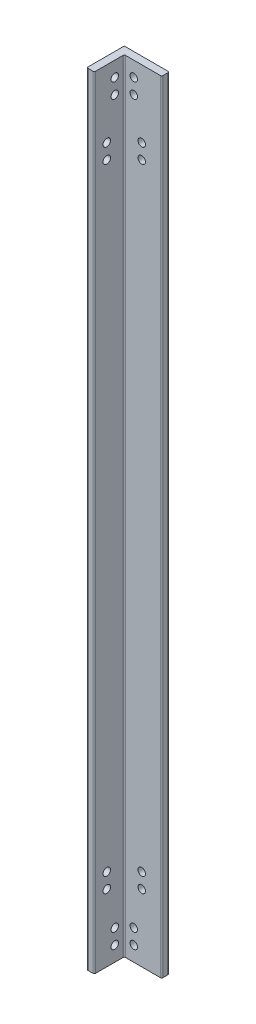
SolidWorks part; units mm, degrees
material "7075-T6 (SN)"
ref_plane "Front Plane" through (0, 0, 0) normal (0, 0, 1) x (1, 0, 0)
ref_plane "Top Plane" through (0, 0, 0) normal (0, 1, 0) x (1, 0, 0)
ref_plane "Right Plane" through (0, 0, 0) normal (1, 0, 0) x (0, 0, -1)
sketch "Sketch1" plane through (0, 0, 0) normal (0, 0, 1) x (1, 0, 0)
  line L0 (-2.6571, 19.3571) -> (-2.6571, -293.6429)
  line L1 (-2.6571, -293.6429) -> (0.3429, -293.6429)
  line L2 (0.3429, -293.6429) -> (0.3429, 19.3571)
  line L3 (0.3429, 19.3571) -> (-2.6571, 19.3571)
  line L4 (0.3429, 19.3571) -> (15.3429, 19.3571)
  line L5 (15.3429, 19.3571) -> (15.3429, -293.6429)
  line L6 (15.3429, -293.6429) -> (0.3429, -293.6429)
  line L7 (0.3429, 19.3571) -> (0.3429, -293.6429)
  circle A0 centre (4.1429, 13.3571) radius 1.5
  circle A1 centre (4.1429, -287.6429) radius 1.5
  circle A2 centre (4.1429, 7.3571) radius 1.5
  circle A3 centre (4.1429, -281.6429) radius 1.5
  circle A4 centre (7.3429, -266.6429) radius 1.5
  circle A5 centre (7.3429, -260.6429) radius 1.5
  circle A6 centre (7.3429, -13.6429) radius 1.5
  circle A7 centre (7.3429, -7.6429) radius 1.5
  dimension "D3" = 6
  dimension "D7" = 3
  dimension "D10" = 3.8
  dimension "D12" = 3.8
  dimension "D4" = 3
  dimension "D5" = 3
  dimension "D6" = 3
  dimension "D17" = 3
  dimension "D18" = 3
  dimension "D22" = 3
  dimension "D23" = 3
  dimension "D1" = 301
  dimension "D2" = 6
  dimension "D8" = 6
  dimension "D9" = 6
  dimension "D11" = 3.8
  dimension "D13" = 3.8
  dimension "D14" = 3
  dimension "D15" = 15
  dimension "D16" = 6
  dimension "D19" = 15
  dimension "D20" = 7
  dimension "D21" = 7
  dimension "D24" = 6
  dimension "D25" = 15
  dimension "D26" = 7
  dimension "D27" = 7
extrude "Boss-Extrude2" add sketch "Sketch1" along normal blind 3 contours L6 L5 L4 L2 A1 A0 region at (7.8685, -137.1429, 0)
extrude "Boss-Extrude3" add sketch "Sketch1<4>" along normal blind 15 contours L2 L3 L0 L1 region at (-1.1571, -137.1429, 0)
sketch "Sketch1<4>" plane through (0, 0, 0) normal (0, 0, 1) x (1, 0, 0) same geometry as "Sketch1"
sketch "Sketch2" plane through (-2.6571, 0, 0) normal (-1, 0, 0) x (0, 0, 1)
  line L0 (15, 19.3571) -> (0, 19.3571) construction
  line L2 (15, -293.6429) -> (0, -293.6429) construction
  line L5 (0, -9.9) -> (0, 9.9) construction
  circle A0 centre (6.8, 13.3571) radius 1.5
  circle A1 centre (6.8, -287.6429) radius 1.5
  circle A2 centre (6.8, -281.6429) radius 1.5
  circle A3 centre (6.8, 7.3571) radius 1.5
  circle A4 centre (10, -266.6429) radius 1.5
  circle A5 centre (10, -260.6429) radius 1.5
  circle A6 centre (10, -13.6429) radius 1.5
  circle A7 centre (10, -7.6429) radius 1.5
  dimension "D1" = 3
  dimension "D4" = 3
  dimension "D7" = 3
  dimension "D12" = 3
  dimension "D15" = 3
  dimension "D16" = 3
  dimension "D23" = 3
  dimension "D24" = 3
  dimension "D2" = 6
  dimension "D3" = 6.8
  dimension "D5" = 6
  dimension "D6" = 6.8
  dimension "D8" = 6
  dimension "D9" = 6.8
  dimension "D10" = 6
  dimension "D11" = 6.8
  dimension "D13" = 10
  dimension "D14" = 10
  dimension "D17" = 15
  dimension "D18" = 6
  dimension "D19" = 10
  dimension "D20" = 10
  dimension "D21" = 6
  dimension "D22" = 15
extrude "Cut-Extrude1" cut sketch "Sketch2" against normal up to next
fillet "Fillet1" radius 0.5 5 edges at (15.3429, -137.1429, 0) (15.3429, -137.1429, 3) (-2.6571, -137.1429, 15) (0.3429, -137.1429, 15) (0.3429, -137.1429, 3)
